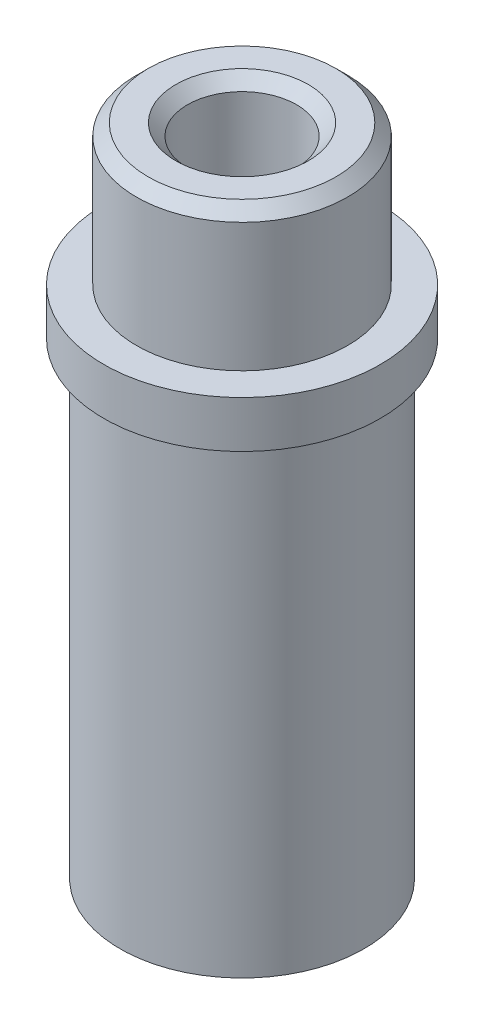
SolidWorks part; units mm, degrees
ref_plane "Front Plane" through (0, 0, 0) normal (0, 0, 1) x (1, 0, 0)
ref_plane "Top Plane" through (0, 0, 0) normal (0, 1, 0) x (1, 0, 0)
ref_plane "Right Plane" through (0, 0, 0) normal (1, 0, 0) x (0, 0, -1)
sketch "Sketch1" plane through (0, 0, 0) normal (0, 0, 1) x (1, 0, 0)
  line L0 (-1.778, 1.5953) -> (-3.4417, 1.5953)
  line L1 (-3.4417, 1.5953) -> (-3.4417, -2.9767)
  line L2 (-3.4417, -2.9767) -> (-4.5085, -2.9767)
  line L3 (-4.5085, -2.9767) -> (-4.5085, -4.5007)
  line L4 (-4.5085, -4.5007) -> (-3.9751, -4.5007)
  line L5 (-3.9751, -4.5007) -> (-3.9751, -19.7407)
  line L6 (-3.9751, -19.7407) -> (0, -19.7407)
  line L7 (0, -19.7407) -> (0, -11.1047)
  line L8 (0, -11.1047) -> (-1.778, -11.1047)
  line L9 (-1.778, -11.1047) -> (-1.778, 1.5953)
  line L10 (0, -11.1047) -> (0, 4.3034) construction
  dimension "D1" = 3.556
  dimension "D2" = 3.4417
  dimension "D3" = 4.572
  dimension "D4" = 12.7
  dimension "D5" = 1.524
  dimension "D6" = 15.24
  dimension "D7" = 4.5085
  dimension "D8" = 3.9751
revolve "Revolve1" add sketch "Sketch1" angle 360 about L10
chamfer "Chamfer1" distance 0.381 angle 45 2 edges at (0, 1.5953, -3.4417) (0, 1.5953, -1.778)
ref_axis "Centerline" through (0, 5.4608, 0) along (0, -1, 0)
